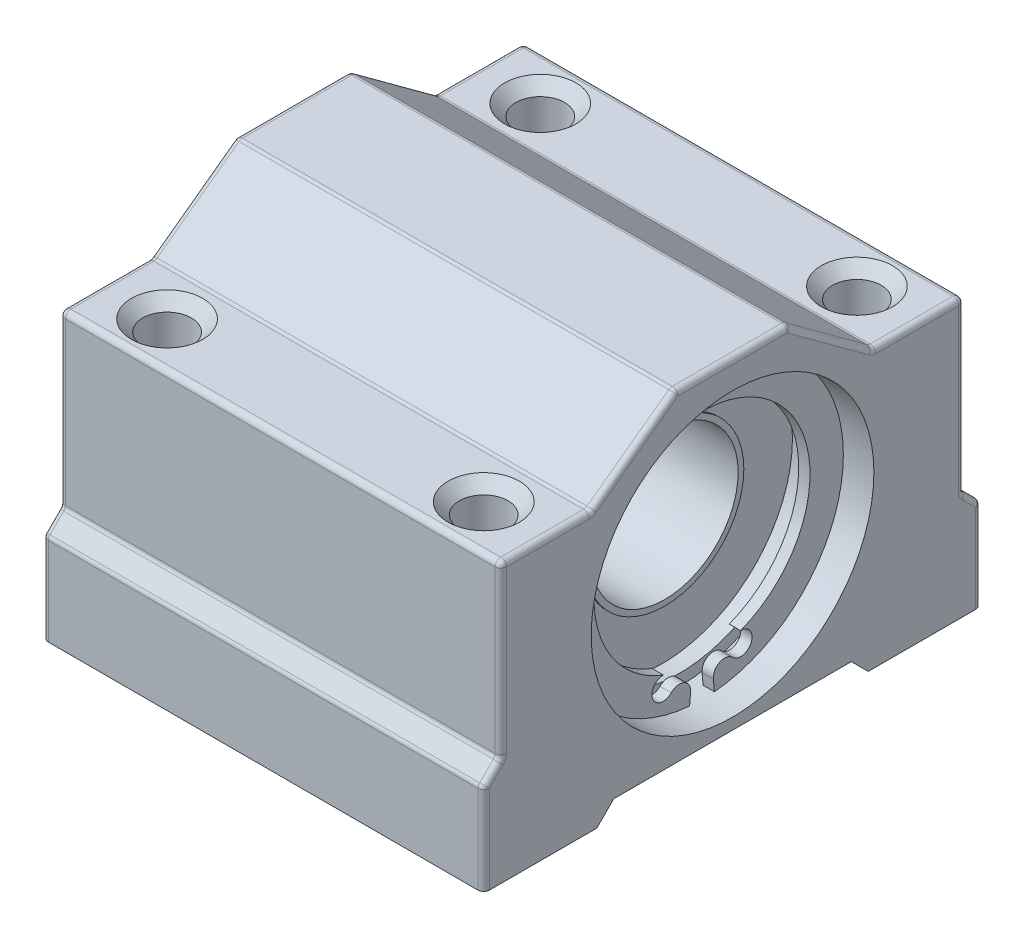
SolidWorks part; units mm, degrees
ref_plane "Front Plane" through (0, 0, 0) normal (0, 0, 1) x (1, 0, 0)
ref_plane "Top Plane" through (0, 0, 0) normal (0, 1, 0) x (1, 0, 0)
ref_plane "Right Plane" through (0, 0, 0) normal (1, 0, 0) x (0, 0, -1)
sketch "Sketch1" plane through (0, 0, 0) normal (1, 0, 0) x (0, 0, -1)
  line L1 (-12, -15) -> (-10.5, -13.5)
  line L2 (-10.5, -13.5) -> (10.5, -13.5)
  line L3 (10.5, -13.5) -> (12, -15)
  line L4 (12, -15) -> (22, -15)
  line L6 (22, -7) -> (20.5, -5.5)
  line L8 (20.5, 9.5) -> (12.5, 9.5)
  line L9 (12.5, 9.5) -> (5, 15)
  line L10 (5, 15) -> (-5, 15)
  line L11 (-5, 15) -> (-12.5, 9.5)
  line L12 (-12.5, 9.5) -> (-20.5, 9.5)
  line L15 (-22, -7) -> (-22, -15)
  line L16 (0, -13.5) -> (0, 15) construction
  line L17 (-16.278, 0) -> (14.0247, 0) construction
  line L18 (-22, -15) -> (-12, -15)
  line L19 (22, -7) -> (22, -15)
  line L20 (-20.5, -5.5) -> (-20.5, 9.5)
  line L21 (20.5, -5.5) -> (20.5, 9.5)
  line L22 (-16.5, 9.5) -> (-16.5, -15) construction
  line L23 (-16.5, -15) -> (16.5, 9.5) construction
  line L24 (16.5, 9.5) -> (16.5, -15) construction
  line L25 (-22, -7) -> (-20.5, -5.5)
  line L26 (-12.5, 0) -> (12.5, 0) construction
  circle A0 centre (0, 0) radius 12.5
  circle A1 centre (0, 0) radius 11.5
  circle A2 centre (0, 0) radius 6.5
  point P18 (0, 15)
  point P23 (0, 0)
  dimension "D12" = 13
  dimension "D1" = 44
  dimension "D2" = 24.5
  dimension "D3" = 15
  dimension "D5" = 30
  dimension "D6" = 33
  dimension "D4" = 8
  dimension "D7" = 1.5
  dimension "D8" = 10
  dimension "D9" = 1.5
  dimension "D10" = 10
  dimension "D11" = 1
extrude "Boss-Extrude1" add sketch "Sketch1" along normal blind 39 contours L25 L15 L18 L1 L2 L3 L4 L19 L6 L21 L8 L9 L10 L11 L12 L20 A0 region at (0, -14.4675, 17)
extrude "Extrude-Thin1" add sketch "Sketch1<4>" along normal blind 32.5 from offset 0.5 separate body thin contours A2 thin type one direction wall 0.5
sketch "Sketch1<4>" plane through (0, 0, 0) normal (1, 0, 0) x (0, 0, -1) same geometry as "Sketch1"
extrude "Boss-Extrude2" add sketch "Sketch1<5>" along normal blind 32 from offset 0.8 contours A1 A2 region at (0, 0, 11.1747)
sketch "Sketch1<5>" plane through (0, 0, 0) normal (1, 0, 0) x (0, 0, -1) same geometry as "Sketch1"
extrude "Boss-Extrude3" add sketch "Sketch1<6>" along normal blind 34 from offset 0.3 contours A0 A1 region at (0, 0, 12.1464)
sketch "Sketch1<6>" plane through (0, 0, 0) normal (1, 0, 0) x (0, 0, -1) same geometry as "Sketch1"
ref_plane "Plane1" through (34.3, 0, 0) normal (1, 0, 0) x (0, 0, -1)
sketch "Sketch3" plane through (34.3, 0, 0) normal (1, 0, 0) x (0, 0, -1)
  line L0 (0, 0) -> (0, -50000) construction
  line L1 (-1.0086, -11.4557) -> (-1.0963, -12.4518)
  line L2 (1.0086, -11.4557) -> (1.0963, -12.4518)
  circle A0 centre (0, 0) radius 12.5 construction
  arc A1 (1.0963, -12.4518) -> (-1.0963, -12.4518) centre (0, 0) ccw
  circle A2 centre (0, 0) radius 11.5 construction
  arc A3 (0, -11.5) -> (1.0086, -11.4557) centre (0, 0) ccw
  arc A4 (-1.0086, -11.4557) -> (-2.7141, -10.6247) centre (-2, -11.3248) ccw
  circle A5 centre (-2, -11.3248) radius 0.25
  arc A6 (-2.2457, -11.2786) -> (-1.7534, -11.3656) centre (0, 0) ccw
  arc A7 (-2.7141, -10.6247) -> (-3.4089, -8.9248) centre (-3.4281, -9.9246) cw
  arc A8 (2.7141, -10.6247) -> (3.4089, -8.9248) centre (3.4281, -9.9246) ccw
  circle A10 centre (2, -11.3248) radius 0.25
  arc A11 (1.0086, -11.4557) -> (2.7141, -10.6247) centre (2, -11.3248) cw
  arc A13 (3.4089, -8.9248) -> (-3.4089, -8.9248) centre (0, 0) ccw
  point P12 (-1.1793, -6.3921)
  dimension "D1" = 0.5
  dimension "D2" = 2
  dimension "D3" = 1
  dimension "D4" = 2
extrude "Boss-Extrude4" add sketch "Sketch3" along normal blind 1 from offset 1 contours A11 A8 A13 A7 A4 L1 A1 L2
fillet "Fillet1" radius 0.5 32 edges at (19.5, -5.5, -20.5) (19.5, -5.5, 20.5) (19.5, -7, 22) (19.5, -7, -22) (19.5, 9.5, -12.5) (19.5, 9.5, 12.5) (19.5, 15, 5) (19.5, 15, -5) (19.5, 9.5, -20.5) (19.5, 9.5, 20.5) (39, 12.25, -8.75) (39, 12.25, 8.75) (39, 2, 20.5) (0, -6.25, 21.25) (0, 12.25, 8.75) (39, -6.25, -21.25) (39, -11, -22) (39, 2, -20.5) (39, 15, 0) (39, 9.5, -16.5) (39, 9.5, 16.5) (39, -6.25, 21.25) (39, -11, 22) (0, -11, -22) (0, -6.25, -21.25) (0, 2, -20.5) (0, 12.25, -8.75) (0, 9.5, -16.5) (0, 15, 0) (0, -11, 22) (0, 2, 20.5) (0, 9.5, 16.5)
sketch "Sketch4" plane through (0, -15, 0) normal (0, -1, 0) x (1, 0, 0)
  line L0 (19.5, 22) -> (19.5, -22) construction
  line L1 (38.5, 22) -> (0.5, 22) construction
  line L2 (38.5, -22) -> (0.5, -22) construction
  line L4 (-4.9444, 16.5) -> (27.0918, 16.5) construction
  line L6 (0, 0) -> (36.1646, 0) construction
  circle A0 centre (5.5, 16.5) radius 2.15
  circle A1 centre (33.5, 16.5) radius 2.15
  circle A2 centre (33.5, -16.5) radius 2.15
  circle A3 centre (5.5, -16.5) radius 2.15
  dimension "D2" = 4.3
  dimension "D1" = 16.5
  dimension "D3" = 28
extrude "Cut-Extrude3" cut sketch "Sketch4" against normal through all
chamfer "Chamfer1" distance 1 angle 45 6 edges at (33.5, 9.5, -18.65) (5.5, 9.5, -18.65) (5.5, 9.5, 14.35) (33.5, 9.5, 14.35) (33.5, -15, 18.65) (5.5, -15, 14.35)
equation "\"D1@Boss-Extrude2\"= \"D1@Boss-Extrude1\" - 2 - 5"
equation "\"D1@Boss-Extrude3\"= \"D1@Boss-Extrude1\" - 5"
equation "\"D1@Sketch4\"= \"D6@Sketch1\" / 2"
equation "\"D1@Extrude-Thin1\"= \"D1@Boss-Extrude3\" - 1.5"
